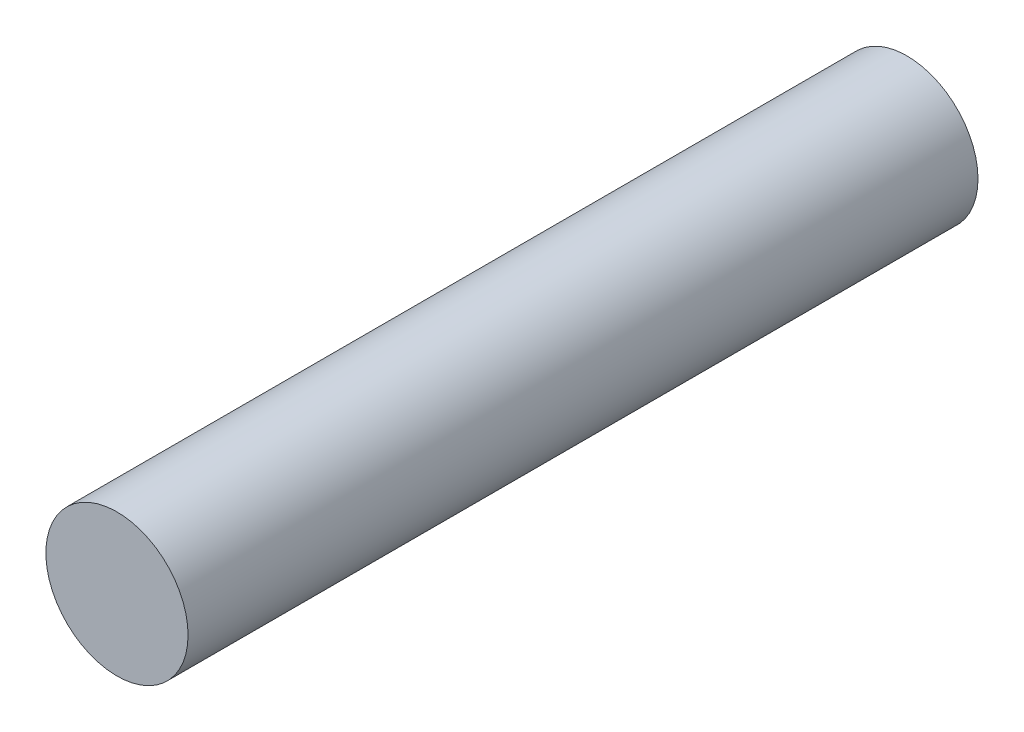
SolidWorks part; units mm, degrees
ref_plane "Front Plane" through (0, 0, 0) normal (0, 0, 1) x (1, 0, 0)
ref_plane "Top Plane" through (0, 0, 0) normal (0, 1, 0) x (1, 0, 0)
ref_plane "Right Plane" through (0, 0, 0) normal (1, 0, 0) x (0, 0, -1)
sketch "Sketch1" plane through (0, 0, 0) normal (0, 0, 1) x (1, 0, 0)
  circle A0 centre (0, 0) radius 2.25
  dimension "D1" = 4.5
extrude "Boss-Extrude1" add sketch "Sketch1" along normal blind 15 and the other way blind 10
sketch "Sketch2" plane through (0, 0, 0) normal (0, 0, 1) x (1, 0, 0)
  circle A0 centre (0, 0) radius 2.5 construction
  dimension "D1" = 5
